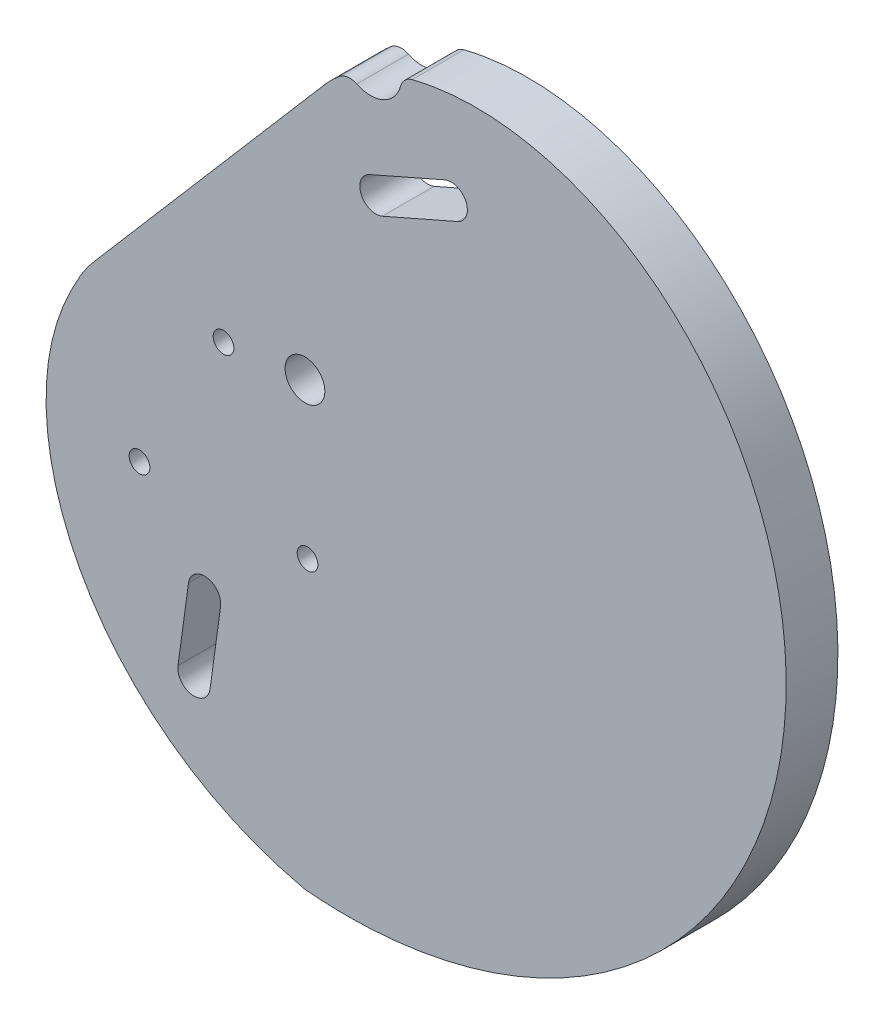
SolidWorks part; units mm, degrees
ref_plane "Front Plane" through (0, 0, 0) normal (0, 0, 1) x (1, 0, 0)
ref_plane "Top Plane" through (0, 0, 0) normal (0, 1, 0) x (1, 0, 0)
ref_plane "Right Plane" through (0, 0, 0) normal (1, 0, 0) x (0, 0, -1)
curve "Curve1"
  spline degree 3 poles (-1.1843, -67.9504, 0) (-0.014, -68.2767, 0) (1.195, -68.3213, 0) (2.3889, -68.4148, 0) (3.5889, -68.4701, 0) (4.791, -68.5105, 0) (5.9959, -68.5295, 0) (7.203, -68.5287, 0) (8.412, -68.5074, 0) (9.6226, -68.4657, 0) (10.8344, -68.4032, 0) (12.047, -68.32, 0) (13.2602, -68.2159, 0) (14.4735, -68.0908, 0) (15.6866, -67.9446, 0) (16.8991, -67.777, 0) (18.1106, -67.5882, 0) (19.3207, -67.3779, 0) (20.529, -67.1461, 0) (21.7351, -66.8927, 0) (22.9386, -66.6176, 0) (24.1392, -66.3208, 0) (25.3362, -66.0022, 0) (26.5295, -65.6619, 0) (27.7184, -65.2996, 0) (28.9026, -64.9155, 0) (30.0816, -64.5096, 0) (31.2551, -64.0817, 0) (32.4225, -63.632, 0) (33.5833, -63.1604, 0) (34.7372, -62.667, 0) (35.8837, -62.1518, 0) (37.0223, -61.6149, 0) (38.1525, -61.0563, 0) (39.2739, -60.4761, 0) (40.3861, -59.8743, 0) (41.4885, -59.2512, 0) (42.5806, -58.6068, 0) (43.6621, -57.9411, 0) (44.7324, -57.2544, 0) (45.791, -56.5468, 0) (46.8375, -55.8184, 0) (47.8714, -55.0695, 0) (48.8923, -54.3001, 0) (49.8996, -53.5105, 0) (50.8929, -52.7009, 0) (51.8717, -51.8715, 0) (52.8356, -51.0225, 0) (53.7841, -50.1542, 0) (54.7166, -49.2668, 0) (55.6329, -48.3607, 0) (56.5323, -47.436, 0) (57.4145, -46.4932, 0) (58.279, -45.5324, 0) (59.1254, -44.554, 0) (59.9531, -43.5583, 0) (60.7619, -42.5458, 0) (61.5512, -41.5167, 0) (62.3207, -40.4714, 0) (63.0698, -39.4103, 0) (63.7983, -38.3338, 0) (64.5057, -37.2423, 0) (65.1916, -36.1362, 0) (65.8556, -35.016, 0) (66.4973, -33.882, 0) (67.1165, -32.7348, 0) (67.7126, -31.5748, 0) (68.2854, -30.4026, 0) (68.8345, -29.2185, 0) (69.3596, -28.023, 0) (69.8603, -26.8168, 0) (70.3364, -25.6003, 0) (70.7876, -24.3741, 0) (71.2134, -23.1386, 0) (71.6138, -21.8945, 0) (71.9884, -20.6423, 0) (72.337, -19.3826, 0) (72.6592, -18.116, 0) (72.955, -16.843, 0) (73.224, -15.5643, 0) (73.4661, -14.2804, 0) (73.6812, -12.992, 0) (73.8689, -11.6997, 0) (74.0292, -10.4042, 0) (74.1619, -9.106, 0) (74.2669, -7.8058, 0) (74.3441, -6.5043, 0) (74.3933, -5.2021, 0) (74.4146, -3.9, 0) (74.4078, -2.5984, 0) (74.3729, -1.2982, 0) (74.3098, -0.0001, 0) (74.2186, 1.2954, 0) (74.0993, 2.5875, 0) (73.9518, 3.8756, 0) (73.7762, 5.1589, 0) (73.5725, 6.4367, 0) (73.3409, 7.7084, 0) (73.0814, 8.9732, 0) (72.7942, 10.2305, 0) (72.4792, 11.4795, 0) (72.1368, 12.7196, 0) (71.767, 13.95, 0) (71.3701, 15.1701, 0) (70.9462, 16.3792, 0) (70.4955, 17.5765, 0) (70.0184, 18.7613, 0) (69.515, 19.9331, 0) (68.9856, 21.091, 0) (68.4305, 22.2344, 0) (67.85, 23.3626, 0) (67.2445, 24.475, 0) (66.6143, 25.5709, 0) (65.9598, 26.6495, 0) (65.2813, 27.7103, 0) (64.5793, 28.7526, 0) (63.8542, 29.7758, 0) (63.1064, 30.7792, 0) (62.3364, 31.7621, 0) (61.5447, 32.7241, 0) (60.7318, 33.6643, 0) (59.8981, 34.5824, 0) (59.0442, 35.4776, 0) (58.1707, 36.3494, 0) (57.2782, 37.1972, 0) (56.3671, 38.0204, 0) (55.4383, 38.8186, 0) (54.4923, 39.5913, 0) (53.53, 40.3381, 0) (52.552, 41.0585, 0) (51.5591, 41.7521, 0) (50.552, 42.4186, 0) (49.5315, 43.0576, 0) (48.4984, 43.6687, 0) (47.4535, 44.2516, 0) (46.3974, 44.8061, 0) (45.3311, 45.3318, 0) (44.2553, 45.8284, 0) (43.1709, 46.2958, 0) (42.0786, 46.7338, 0) (40.9793, 47.1421, 0) (39.8737, 47.5205, 0) (38.7628, 47.869, 0) (37.6473, 48.1874, 0) (36.5281, 48.4755, 0) (35.4061, 48.7334, 0) (34.282, 48.961, 0) (33.1567, 49.1581, 0) (32.031, 49.3249, 0) (30.9059, 49.4613, 0) (29.7821, 49.5673, 0) (28.6604, 49.6431, 0) (27.5418, 49.6886, 0) (26.427, 49.7041, 0) (25.3169, 49.6895, 0) (24.2124, 49.6451, 0) (23.1141, 49.571, 0) (22.0231, 49.4674, 0) (20.94, 49.3346, 0) (19.8657, 49.1727, 0) (18.801, 48.982, 0) (17.7468, 48.7628, 0) (16.7037, 48.5154, 0) (15.6726, 48.2401, 0) (14.6543, 47.9373, 0) (13.6495, 47.6073, 0) (12.659, 47.2504, 0) (11.6836, 46.8672, 0) (10.7239, 46.458, 0) (9.7807, 46.0233, 0) (8.8547, 45.5635, 0) (7.9467, 45.0791, 0) (7.0573, 44.5706, 0) (6.1871, 44.0386, 0) (5.3369, 43.4835, 0) (4.5074, 42.906, 0) (3.699, 42.3065, 0) (2.9126, 41.6858, 0) (2.1491, 41.0448, 0) (1.4087, 40.3857, 0) (0.692, 39.711, 0) (-0.0007, 39.0233, 0) (-0.6692, 38.3252, 0) (-1.3135, 37.6192, 0) (-1.9336, 36.908, 0) (-2.5298, 36.194, 0) (-3.1024, 35.4799, 0) (-3.6521, 34.7682, 0) (-4.1795, 34.0612, 0) (-4.6854, 33.3616, 0) (-5.1709, 32.6716, 0) (-5.637, 31.9937, 0) (-6.085, 31.3301, 0) (-6.5163, 30.6831, 0) (-6.9325, 30.0548, 0) (-7.3352, 29.4474, 0) (-7.7263, 28.8629, 0) (-8.1078, 28.3032, 0) (-8.4816, 27.77, 0) (-8.8501, 27.2652, 0) (-9.216, 26.7897, 0) (-9.5801, 26.3424, 0) (-9.9432, 25.9213, 0) (-10.3062, 25.5243, 0) (-10.6698, 25.1494, 0) (-11.0346, 24.7946, 0) (-11.4009, 24.4578, 0) (-11.7691, 24.1369, 0) (-12.1394, 23.8299, 0) (-12.5117, 23.5348, 0) (-12.8861, 23.2497, 0) (-13.2622, 22.9725, 0) (-13.6397, 22.7014, 0) (-14.0182, 22.4345, 0) (-14.3971, 22.1699, 0) (-14.7757, 21.906, 0) (-15.1531, 21.6409, 0) (-15.5285, 21.3732, 0) (-15.9009, 21.1012, 0) (-16.269, 20.8234, 0) (-16.6317, 20.5384, 0) (-16.9875, 20.2449, 0) (-17.3351, 19.9417, 0) (-17.6745, 19.6295, 0) (-18.0059, 19.3089, 0) (-18.3295, 18.9807, 0) (-18.6455, 18.6455, 0) (-18.9542, 18.3039, 0) (-19.2559, 17.9565, 0) (-19.5509, 17.6038, 0) (-19.8396, 17.2464, 0) (-20.1224, 16.8848, 0) (-20.3997, 16.5195, 0) (-20.672, 16.1508, 0) (-20.9397, 15.7793, 0) (-21.2033, 15.4052, 0) (-21.4634, 15.0289, 0) (-21.7205, 14.6507, 0) (-21.9753, 14.2708, 0) (-22.2281, 13.8895, 0) (-22.4798, 13.507, 0) (-22.7308, 13.1233, 0) (-22.9819, 12.7386, 0) (-23.2336, 12.3529, 0) (-23.4866, 11.9663, 0) (-23.7416, 11.5787, 0) (-23.9993, 11.19, 0) (-24.2602, 10.8001, 0) (-24.5251, 10.4088, 0) (-24.7947, 10.016, 0) (-25.0696, 9.6214, 0) (-25.3504, 9.2246, 0) (-25.6379, 8.8254, 0) (-25.9327, 8.4234, 0) (-26.2354, 8.018, 0) (-26.5467, 7.609, 0) (-26.8672, 7.1956, 0) (-27.1974, 6.7776, 0) (-27.537, 6.3539, 0) (-27.8856, 5.9238, 0) (-28.2424, 5.4864, 0) (-28.6069, 5.0408, 0) (-28.9783, 4.5865, 0) (-29.3562, 4.1226, 0) (-29.7396, 3.6485, 0) (-30.1278, 3.1637, 0) (-30.5202, 2.6674, 0) (-30.9158, 2.1592, 0) (-31.314, 1.6386, 0) (-31.7137, 1.1051, 0) (-32.1143, 0.5583, 0) (-32.5148, -0.0021, 0) (-32.9143, -0.5765, 0) (-33.3119, -1.1651, 0) (-33.7067, -1.7682, 0) (-34.0978, -2.3859, 0) (-34.4843, -3.0184, 0) (-34.8652, -3.6658, 0) (-35.2396, -4.3281, 0) (-35.6066, -5.0053, 0) (-35.9651, -5.6973, 0) (-36.3143, -6.404, 0) (-36.6531, -7.1254, 0) (-36.9808, -7.8611, 0) (-37.2963, -8.611, 0) (-37.5988, -9.3748, 0) (-37.8873, -10.1521, 0) (-38.1609, -10.9426, 0) (-38.4187, -11.7459, 0) (-38.66, -12.5613, 0) (-38.8837, -13.3886, 0) (-39.0892, -14.2271, 0) (-39.2755, -15.0762, 0) (-39.4422, -15.9354, 0) (-39.589, -16.8043, 0) (-39.7155, -17.6823, 0) (-39.8215, -18.5689, 0) (-39.9067, -19.4636, 0) (-39.9709, -20.366, 0) (-40.0137, -21.2755, 0) (-40.035, -22.1916, 0) (-40.0345, -23.1138, 0) (-40.0119, -24.0415, 0) (-39.9672, -24.9742, 0) (-39.9002, -25.9114, 0) (-39.8105, -26.8525, 0) (-39.6982, -27.7969, 0) (-39.563, -28.7442, 0) (-39.4048, -29.6936, 0) (-39.2235, -30.6448, 0) (-39.019, -31.597, 0) (-38.7911, -32.5497, 0) (-38.5399, -33.5023, 0) (-38.2653, -34.4543, 0) (-37.9672, -35.4051, 0) (-37.6456, -36.354, 0) (-37.3004, -37.3005, 0) (-36.9317, -38.2441, 0) (-36.5395, -39.184, 0) (-36.1238, -40.1197, 0) (-35.6847, -41.0507, 0) (-35.2221, -41.9763, 0) (-34.7363, -42.896, 0) (-34.2272, -43.8091, 0) (-33.695, -44.715, 0) (-33.1398, -45.6133, 0) (-32.5617, -46.5032, 0) (-31.9609, -47.3843, 0) (-31.3375, -48.2559, 0) (-30.6917, -49.1174, 0) (-30.0238, -49.9683, 0) (-29.3338, -50.808, 0) (-28.6221, -51.636, 0) (-27.8888, -52.4517, 0) (-27.1343, -53.2545, 0) (-26.3587, -54.0439, 0) (-25.5624, -54.8193, 0) (-24.7457, -55.5802, 0) (-23.9088, -56.3261, 0) (-23.0521, -57.0564, 0) (-22.1759, -57.7707, 0) (-21.2805, -58.4684, 0) (-20.3664, -59.149, 0) (-19.4339, -59.812, 0) (-18.4833, -60.4569, 0) (-17.5151, -61.0833, 0) (-16.5298, -61.6908, 0) (-15.5276, -62.2787, 0) (-14.5091, -62.8467, 0) (-13.4747, -63.3944, 0) (-12.4248, -63.9213, 0) (-11.36, -64.4271, 0) (-10.2807, -64.9112, 0) (-9.1874, -65.3733, 0) (-8.0806, -65.8131, 0) (-6.9608, -66.2301, 0) (-5.8286, -66.6239, 0) (-4.6845, -66.9947, 0) (-3.5289, -67.3403, 0) (-2.3631, -67.6669, 0) (-1.1843, -67.9504, 0) (-0.014, -68.2767, 0) (1.195, -68.3213, 0) knots -0.0101 -0.006743 -0.003377 0 0.00332 0.006645 0.009976 0.013312 0.016655 0.020003 0.023357 0.026716 0.030082 0.033453 0.036831 0.040214 0.043603 0.046998 0.050399 0.053806 0.057218 0.060637 0.064061 0.067491 0.070927 0.074369 0.077816 0.081269 0.084728 0.088192 0.091662 0.095138 0.098619 0.102105 0.105597 0.109094 0.112596 0.116103 0.119615 0.123133 0.126655 0.130182 0.133714 0.137251 0.140792 0.144337 0.147888 0.151442 0.155 0.158563 0.16213 0.1657 0.169275 0.172853 0.176434 0.180019 0.183607 0.187199 0.190793 0.19439 0.19799 0.201593 0.205199 0.208806 0.212416 0.216028 0.219642 0.223258 0.226875 0.230494 0.234115 0.237736 0.241359 0.244982 0.248606 0.252231 0.255856 0.259481 0.263106 0.266731 0.270356 0.273981 0.277605 0.281228 0.28485 0.28847 0.29209 0.295708 0.299324 0.302939 0.306551 0.310161 0.313769 0.317374 0.320976 0.324575 0.328171 0.331763 0.335352 0.338938 0.342519 0.346096 0.349669 0.353237 0.356801 0.360359 0.363913 0.367461 0.371004 0.374541 0.378073 0.381598 0.385117 0.38863 0.392136 0.395636 0.399128 0.402614 0.406092 0.409563 0.413026 0.416482 0.419929 0.423369 0.4268 0.430223 0.433637 0.437043 0.44044 0.443828 0.447206 0.450575 0.453935 0.457284 0.460624 0.463953 0.467272 0.47058 0.473877 0.477164 0.480439 0.483703 0.486955 0.490196 0.493426 0.496643 0.499848 0.503042 0.506223 0.509391 0.512547 0.515691 0.518822 0.52194 0.525045 0.528137 0.531216 0.534282 0.537335 0.540375 0.543401 0.546414 0.549414 0.5524 0.555374 0.558333 0.56128 0.564213 0.567133 0.57004 0.572933 0.575814 0.578681 0.581535 0.584377 0.587205 0.590021 0.592825 0.595616 0.598394 0.60116 0.603911 0.606642 0.60935 0.612032 0.614684 0.617303 0.619884 0.622424 0.62492 0.627367 0.629763 0.632104 0.634387 0.636609 0.638767 0.640858 0.64288 0.644831 0.64671 0.648517 0.65025 0.651911 0.653509 0.655048 0.656538 0.657984 0.659394 0.660772 0.662125 0.663458 0.664774 0.666078 0.667373 0.668662 0.669946 0.671227 0.672507 0.673786 0.675065 0.676344 0.677623 0.678903 0.680182 0.681461 0.68274 0.684019 0.685298 0.686575 0.687853 0.689129 0.690404 0.691679 0.692952 0.694224 0.695495 0.696765 0.698035 0.699304 0.700572 0.70184 0.703109 0.704379 0.705651 0.706925 0.708202 0.709483 0.71077 0.712063 0.713364 0.714674 0.715995 0.717328 0.718676 0.72004 0.721422 0.722825 0.72425 0.7257 0.727177 0.728683 0.730218 0.731784 0.73338 0.735008 0.736668 0.738359 0.740082 0.741837 0.743623 0.745441 0.747291 0.749171 0.751082 0.753022 0.754993 0.756992 0.759021 0.761077 0.76316 0.765271 0.767407 0.769569 0.771756 0.773967 0.776201 0.778458 0.780736 0.783036 0.785357 0.787697 0.790056 0.792433 0.794828 0.797239 0.799666 0.80211 0.804571 0.807047 0.80954 0.812049 0.814575 0.817116 0.819674 0.822248 0.824838 0.827444 0.830066 0.832704 0.835358 0.838027 0.840713 0.843414 0.846131 0.848864 0.851612 0.854376 0.857155 0.859949 0.862759 0.865584 0.868424 0.871279 0.874149 0.877033 0.879933 0.882847 0.885776 0.88872 0.891678 0.89465 0.897636 0.900637 0.903651 0.906679 0.909721 0.912777 0.915847 0.91893 0.922026 0.925135 0.928258 0.931393 0.934541 0.937702 0.940876 0.944062 0.947261 0.950471 0.953694 0.956929 0.960175 0.963433 0.966703 0.969984 0.973276 0.976579 0.979893 0.983218 0.986554 0.9899 0.993257 0.996623 1 1.00332 1.006645 1.009976 periodic
sketch "Sketch1" plane through (0, 0, 0) normal (0, 0, 1) x (1, 0, 0)
  line L0 (10.9805, 30.1851) -> (22.6104, 35.2876) construction
  line L1 (9.976, 32.4744) -> (21.6059, 37.5769)
  line L2 (11.9849, 27.8957) -> (23.6148, 32.9983)
  line L3 (10.7688, 46.4724) -> (16.7954, 32.7363) construction
  line L4 (10.1171, 47.9579) -> (5.632, 46.1692) construction
  line L5 (14.4291, 50.1309) -> (10.1171, 47.9579) construction
  circle A0 centre (0, 0) radius 3.075
  arc A1 (9.976, 32.4744) -> (11.9849, 27.8957) centre (10.9805, 30.1851) ccw
  arc A2 (23.6148, 32.9983) -> (21.6059, 37.5769) centre (22.6104, 35.2876) ccw
  arc A3 (5.632, 46.1692) -> (14.4291, 50.1309) centre (10.1171, 47.9579) ccw
  spline S0 degree 3 poles (-1.1843, -67.9504) (-0.014, -68.2767) (1.195, -68.3213) (2.3889, -68.4148) (3.5889, -68.4701) (4.791, -68.5105) (5.9959, -68.5295) (7.203, -68.5287) (8.412, -68.5074) (9.6226, -68.4657) (10.8344, -68.4032) (12.047, -68.32) (13.2602, -68.2159) (14.4735, -68.0908) (15.6866, -67.9446) (16.8991, -67.777) (18.1106, -67.5882) (19.3207, -67.3779) (20.529, -67.1461) (21.7351, -66.8927) (22.9386, -66.6176) (24.1392, -66.3208) (25.3362, -66.0022) (26.5295, -65.6619) (27.7184, -65.2996) (28.9026, -64.9155) (30.0816, -64.5096) (31.2551, -64.0817) (32.4225, -63.632) (33.5833, -63.1604) (34.7372, -62.667) (35.8837, -62.1518) (37.0223, -61.6149) (38.1525, -61.0563) (39.2739, -60.4761) (40.3861, -59.8743) (41.4885, -59.2512) (42.5806, -58.6068) (43.6621, -57.9411) (44.7324, -57.2544) (45.791, -56.5468) (46.8375, -55.8184) (47.8714, -55.0695) (48.8923, -54.3001) (49.8996, -53.5105) (50.8929, -52.7009) (51.8717, -51.8715) (52.8356, -51.0225) (53.7841, -50.1542) (54.7166, -49.2668) (55.6329, -48.3607) (56.5323, -47.436) (57.4145, -46.4932) (58.279, -45.5324) (59.1254, -44.554) (59.9531, -43.5583) (60.7619, -42.5458) (61.5512, -41.5167) (62.3207, -40.4714) (63.0698, -39.4103) (63.7983, -38.3338) (64.5057, -37.2423) (65.1916, -36.1362) (65.8556, -35.016) (66.4973, -33.882) (67.1165, -32.7348) (67.7126, -31.5748) (68.2854, -30.4026) (68.8345, -29.2185) (69.3596, -28.023) (69.8603, -26.8168) (70.3364, -25.6003) (70.7876, -24.3741) (71.2134, -23.1386) (71.6138, -21.8945) (71.9884, -20.6423) (72.337, -19.3826) (72.6592, -18.116) (72.955, -16.843) (73.224, -15.5643) (73.4661, -14.2804) (73.6812, -12.992) (73.8689, -11.6997) (74.0292, -10.4042) (74.1619, -9.106) (74.2669, -7.8058) (74.3441, -6.5043) (74.3933, -5.2021) (74.4146, -3.9) (74.4078, -2.5984) (74.3729, -1.2982) (74.3098, -0.0001) (74.2186, 1.2954) (74.0993, 2.5875) (73.9518, 3.8756) (73.7762, 5.1589) (73.5725, 6.4367) (73.3409, 7.7084) (73.0814, 8.9732) (72.7942, 10.2305) (72.4792, 11.4795) (72.1368, 12.7196) (71.767, 13.95) (71.3701, 15.1701) (70.9462, 16.3792) (70.4955, 17.5765) (70.0184, 18.7613) (69.515, 19.9331) (68.9856, 21.091) (68.4305, 22.2344) (67.85, 23.3626) (67.2445, 24.475) (66.6143, 25.5709) (65.9598, 26.6495) (65.2813, 27.7103) (64.5793, 28.7526) (63.8542, 29.7758) (63.1064, 30.7792) (62.3364, 31.7621) (61.5447, 32.7241) (60.7318, 33.6643) (59.8981, 34.5824) (59.0442, 35.4776) (58.1707, 36.3494) (57.2782, 37.1972) (56.3671, 38.0204) (55.4383, 38.8186) (54.4923, 39.5913) (53.53, 40.3381) (52.552, 41.0585) (51.5591, 41.7521) (50.552, 42.4186) (49.5315, 43.0576) (48.4984, 43.6687) (47.4535, 44.2516) (46.3974, 44.8061) (45.3311, 45.3318) (44.2553, 45.8284) (43.1709, 46.2958) (42.0786, 46.7338) (40.9793, 47.1421) (39.8737, 47.5205) (38.7628, 47.869) (37.6473, 48.1874) (36.5281, 48.4755) (35.4061, 48.7334) (34.282, 48.961) (33.1567, 49.1581) (32.031, 49.3249) (30.9059, 49.4613) (29.7821, 49.5673) (28.6604, 49.6431) (27.5418, 49.6886) (26.427, 49.7041) (25.3169, 49.6895) (24.2124, 49.6451) (23.1141, 49.571) (22.0231, 49.4674) (20.94, 49.3346) (19.8657, 49.1727) (18.801, 48.982) (17.7468, 48.7628) (16.7037, 48.5154) (15.6726, 48.2401) (14.6543, 47.9373) (13.6495, 47.6073) (12.659, 47.2504) (11.6836, 46.8672) (10.7239, 46.458) (9.7807, 46.0233) (8.8547, 45.5635) (7.9467, 45.0791) (7.0573, 44.5706) (6.1871, 44.0386) (5.3369, 43.4835) (4.5074, 42.906) (3.699, 42.3065) (2.9126, 41.6858) (2.1491, 41.0448) (1.4087, 40.3857) (0.692, 39.711) (-0.0007, 39.0233) (-0.6692, 38.3252) (-1.3135, 37.6192) (-1.9336, 36.908) (-2.5298, 36.194) (-3.1024, 35.4799) (-3.6521, 34.7682) (-4.1795, 34.0612) (-4.6854, 33.3616) (-5.1709, 32.6716) (-5.637, 31.9937) (-6.085, 31.3301) (-6.5163, 30.6831) (-6.9325, 30.0548) (-7.3352, 29.4474) (-7.7263, 28.8629) (-8.1078, 28.3032) (-8.4816, 27.77) (-8.8501, 27.2652) (-9.216, 26.7897) (-9.5801, 26.3424) (-9.9432, 25.9213) (-10.3062, 25.5243) (-10.6698, 25.1494) (-11.0346, 24.7946) (-11.4009, 24.4578) (-11.7691, 24.1369) (-12.1394, 23.8299) (-12.5117, 23.5348) (-12.8861, 23.2497) (-13.2622, 22.9725) (-13.6397, 22.7014) (-14.0182, 22.4345) (-14.3971, 22.1699) (-14.7757, 21.906) (-15.1531, 21.6409) (-15.5285, 21.3732) (-15.9009, 21.1012) (-16.269, 20.8234) (-16.6317, 20.5384) (-16.9875, 20.2449) (-17.3351, 19.9417) (-17.6745, 19.6295) (-18.0059, 19.3089) (-18.3295, 18.9807) (-18.6455, 18.6455) (-18.9542, 18.3039) (-19.2559, 17.9565) (-19.5509, 17.6038) (-19.8396, 17.2464) (-20.1224, 16.8848) (-20.3997, 16.5195) (-20.672, 16.1508) (-20.9397, 15.7793) (-21.2033, 15.4052) (-21.4634, 15.0289) (-21.7205, 14.6507) (-21.9753, 14.2708) (-22.2281, 13.8895) (-22.4798, 13.507) (-22.7308, 13.1233) (-22.9819, 12.7386) (-23.2336, 12.3529) (-23.4866, 11.9663) (-23.7416, 11.5787) (-23.9993, 11.19) (-24.2602, 10.8001) (-24.5251, 10.4088) (-24.7947, 10.016) (-25.0696, 9.6214) (-25.3504, 9.2246) (-25.6379, 8.8254) (-25.9327, 8.4234) (-26.2354, 8.018) (-26.5467, 7.609) (-26.8672, 7.1956) (-27.1974, 6.7776) (-27.537, 6.3539) (-27.8856, 5.9238) (-28.2424, 5.4864) (-28.6069, 5.0408) (-28.9783, 4.5865) (-29.3562, 4.1226) (-29.7396, 3.6485) (-30.1278, 3.1637) (-30.5202, 2.6674) (-30.9158, 2.1592) (-31.314, 1.6386) (-31.7137, 1.1051) (-32.1143, 0.5583) (-32.5148, -0.0021) (-32.9143, -0.5765) (-33.3119, -1.1651) (-33.7067, -1.7682) (-34.0978, -2.3859) (-34.4843, -3.0184) (-34.8652, -3.6658) (-35.2396, -4.3281) (-35.6066, -5.0053) (-35.9651, -5.6973) (-36.3143, -6.404) (-36.6531, -7.1254) (-36.9808, -7.8611) (-37.2963, -8.611) (-37.5988, -9.3748) (-37.8873, -10.1521) (-38.1609, -10.9426) (-38.4187, -11.7459) (-38.66, -12.5613) (-38.8837, -13.3886) (-39.0892, -14.2271) (-39.2755, -15.0762) (-39.4422, -15.9354) (-39.589, -16.8043) (-39.7155, -17.6823) (-39.8215, -18.5689) (-39.9067, -19.4636) (-39.9709, -20.366) (-40.0137, -21.2755) (-40.035, -22.1916) (-40.0345, -23.1138) (-40.0119, -24.0415) (-39.9672, -24.9742) (-39.9002, -25.9114) (-39.8105, -26.8525) (-39.6982, -27.7969) (-39.563, -28.7442) (-39.4048, -29.6936) (-39.2235, -30.6448) (-39.019, -31.597) (-38.7911, -32.5497) (-38.5399, -33.5023) (-38.2653, -34.4543) (-37.9672, -35.4051) (-37.6456, -36.354) (-37.3004, -37.3005) (-36.9317, -38.2441) (-36.5395, -39.184) (-36.1238, -40.1197) (-35.6847, -41.0507) (-35.2221, -41.9763) (-34.7363, -42.896) (-34.2272, -43.8091) (-33.695, -44.715) (-33.1398, -45.6133) (-32.5617, -46.5032) (-31.9609, -47.3843) (-31.3375, -48.2559) (-30.6917, -49.1174) (-30.0238, -49.9683) (-29.3338, -50.808) (-28.6221, -51.636) (-27.8888, -52.4517) (-27.1343, -53.2545) (-26.3587, -54.0439) (-25.5624, -54.8193) (-24.7457, -55.5802) (-23.9088, -56.3261) (-23.0521, -57.0564) (-22.1759, -57.7707) (-21.2805, -58.4684) (-20.3664, -59.149) (-19.4339, -59.812) (-18.4833, -60.4569) (-17.5151, -61.0833) (-16.5298, -61.6908) (-15.5276, -62.2787) (-14.5091, -62.8467) (-13.4747, -63.3944) (-12.4248, -63.9213) (-11.36, -64.4271) (-10.2807, -64.9112) (-9.1874, -65.3733) (-8.0806, -65.8131) (-6.9608, -66.2301) (-5.8286, -66.6239) (-4.6845, -66.9947) (-3.5289, -67.3403) (-2.3631, -67.6669) (-1.1843, -67.9504) (-0.014, -68.2767) (1.195, -68.3213) knots -0.0101 -0.006743 -0.003377 0 0.00332 0.006645 0.009976 0.013312 0.016655 0.020003 0.023357 0.026716 0.030082 0.033453 0.036831 0.040214 0.043603 0.046998 0.050399 0.053806 0.057218 0.060637 0.064061 0.067491 0.070927 0.074369 0.077816 0.081269 0.084728 0.088192 0.091662 0.095138 0.098619 0.102105 0.105597 0.109094 0.112596 0.116103 0.119615 0.123133 0.126655 0.130182 0.133714 0.137251 0.140792 0.144337 0.147888 0.151442 0.155 0.158563 0.16213 0.1657 0.169275 0.172853 0.176434 0.180019 0.183607 0.187199 0.190793 0.19439 0.19799 0.201593 0.205199 0.208806 0.212416 0.216028 0.219642 0.223258 0.226875 0.230494 0.234115 0.237736 0.241359 0.244982 0.248606 0.252231 0.255856 0.259481 0.263106 0.266731 0.270356 0.273981 0.277605 0.281228 0.28485 0.28847 0.29209 0.295708 0.299324 0.302939 0.306551 0.310161 0.313769 0.317374 0.320976 0.324575 0.328171 0.331763 0.335352 0.338938 0.342519 0.346096 0.349669 0.353237 0.356801 0.360359 0.363913 0.367461 0.371004 0.374541 0.378073 0.381598 0.385117 0.38863 0.392136 0.395636 0.399128 0.402614 0.406092 0.409563 0.413026 0.416482 0.419929 0.423369 0.4268 0.430223 0.433637 0.437043 0.44044 0.443828 0.447206 0.450575 0.453935 0.457284 0.460624 0.463953 0.467272 0.47058 0.473877 0.477164 0.480439 0.483703 0.486955 0.490196 0.493426 0.496643 0.499848 0.503042 0.506223 0.509391 0.512547 0.515691 0.518822 0.52194 0.525045 0.528137 0.531216 0.534282 0.537335 0.540375 0.543401 0.546414 0.549414 0.5524 0.555374 0.558333 0.56128 0.564213 0.567133 0.57004 0.572933 0.575814 0.578681 0.581535 0.584377 0.587205 0.590021 0.592825 0.595616 0.598394 0.60116 0.603911 0.606642 0.60935 0.612032 0.614684 0.617303 0.619884 0.622424 0.62492 0.627367 0.629763 0.632104 0.634387 0.636609 0.638767 0.640858 0.64288 0.644831 0.64671 0.648517 0.65025 0.651911 0.653509 0.655048 0.656538 0.657984 0.659394 0.660772 0.662125 0.663458 0.664774 0.666078 0.667373 0.668662 0.669946 0.671227 0.672507 0.673786 0.675065 0.676344 0.677623 0.678903 0.680182 0.681461 0.68274 0.684019 0.685298 0.686575 0.687853 0.689129 0.690404 0.691679 0.692952 0.694224 0.695495 0.696765 0.698035 0.699304 0.700572 0.70184 0.703109 0.704379 0.705651 0.706925 0.708202 0.709483 0.71077 0.712063 0.713364 0.714674 0.715995 0.717328 0.718676 0.72004 0.721422 0.722825 0.72425 0.7257 0.727177 0.728683 0.730218 0.731784 0.73338 0.735008 0.736668 0.738359 0.740082 0.741837 0.743623 0.745441 0.747291 0.749171 0.751082 0.753022 0.754993 0.756992 0.759021 0.761077 0.76316 0.765271 0.767407 0.769569 0.771756 0.773967 0.776201 0.778458 0.780736 0.783036 0.785357 0.787697 0.790056 0.792433 0.794828 0.797239 0.799666 0.80211 0.804571 0.807047 0.80954 0.812049 0.814575 0.817116 0.819674 0.822248 0.824838 0.827444 0.830066 0.832704 0.835358 0.838027 0.840713 0.843414 0.846131 0.848864 0.851612 0.854376 0.857155 0.859949 0.862759 0.865584 0.868424 0.871279 0.874149 0.877033 0.879933 0.882847 0.885776 0.88872 0.891678 0.89465 0.897636 0.900637 0.903651 0.906679 0.909721 0.912777 0.915847 0.91893 0.922026 0.925135 0.928258 0.931393 0.934541 0.937702 0.940876 0.944062 0.947261 0.950471 0.953694 0.956929 0.960175 0.963433 0.966703 0.969984 0.973276 0.976579 0.979893 0.983218 0.986554 0.9899 0.993257 0.996623 1 1.00332 1.006645 1.009976 only from (0, -68.2309) to (0, -68.2309) construction
  spline S1 degree 3 poles (-1.1843, -67.9504) (-0.014, -68.2767) (1.195, -68.3213) (2.3889, -68.4148) (3.5889, -68.4701) (4.791, -68.5105) (5.9959, -68.5295) (7.203, -68.5287) (8.412, -68.5074) (9.6226, -68.4657) (10.8344, -68.4032) (12.047, -68.32) (13.2602, -68.2159) (14.4735, -68.0908) (15.6866, -67.9446) (16.8991, -67.777) (18.1106, -67.5882) (19.3207, -67.3779) (20.529, -67.1461) (21.7351, -66.8927) (22.9386, -66.6176) (24.1392, -66.3208) (25.3362, -66.0022) (26.5295, -65.6619) (27.7184, -65.2996) (28.9026, -64.9155) (30.0816, -64.5096) (31.2551, -64.0817) (32.4225, -63.632) (33.5833, -63.1604) (34.7372, -62.667) (35.8837, -62.1518) (37.0223, -61.6149) (38.1525, -61.0563) (39.2739, -60.4761) (40.3861, -59.8743) (41.4885, -59.2512) (42.5806, -58.6068) (43.6621, -57.9411) (44.7324, -57.2544) (45.791, -56.5468) (46.8375, -55.8184) (47.8714, -55.0695) (48.8923, -54.3001) (49.8996, -53.5105) (50.8929, -52.7009) (51.8717, -51.8715) (52.8356, -51.0225) (53.7841, -50.1542) (54.7166, -49.2668) (55.6329, -48.3607) (56.5323, -47.436) (57.4145, -46.4932) (58.279, -45.5324) (59.1254, -44.554) (59.9531, -43.5583) (60.7619, -42.5458) (61.5512, -41.5167) (62.3207, -40.4714) (63.0698, -39.4103) (63.7983, -38.3338) (64.5057, -37.2423) (65.1916, -36.1362) (65.8556, -35.016) (66.4973, -33.882) (67.1165, -32.7348) (67.7126, -31.5748) (68.2854, -30.4026) (68.8345, -29.2185) (69.3596, -28.023) (69.8603, -26.8168) (70.3364, -25.6003) (70.7876, -24.3741) (71.2134, -23.1386) (71.6138, -21.8945) (71.9884, -20.6423) (72.337, -19.3826) (72.6592, -18.116) (72.955, -16.843) (73.224, -15.5643) (73.4661, -14.2804) (73.6812, -12.992) (73.8689, -11.6997) (74.0292, -10.4042) (74.1619, -9.106) (74.2669, -7.8058) (74.3441, -6.5043) (74.3933, -5.2021) (74.4146, -3.9) (74.4078, -2.5984) (74.3729, -1.2982) (74.3098, -0.0001) (74.2186, 1.2954) (74.0993, 2.5875) (73.9518, 3.8756) (73.7762, 5.1589) (73.5725, 6.4367) (73.3409, 7.7084) (73.0814, 8.9732) (72.7942, 10.2305) (72.4792, 11.4795) (72.1368, 12.7196) (71.767, 13.95) (71.3701, 15.1701) (70.9462, 16.3792) (70.4955, 17.5765) (70.0184, 18.7613) (69.515, 19.9331) (68.9856, 21.091) (68.4305, 22.2344) (67.85, 23.3626) (67.2445, 24.475) (66.6143, 25.5709) (65.9598, 26.6495) (65.2813, 27.7103) (64.5793, 28.7526) (63.8542, 29.7758) (63.1064, 30.7792) (62.3364, 31.7621) (61.5447, 32.7241) (60.7318, 33.6643) (59.8981, 34.5824) (59.0442, 35.4776) (58.1707, 36.3494) (57.2782, 37.1972) (56.3671, 38.0204) (55.4383, 38.8186) (54.4923, 39.5913) (53.53, 40.3381) (52.552, 41.0585) (51.5591, 41.7521) (50.552, 42.4186) (49.5315, 43.0576) (48.4984, 43.6687) (47.4535, 44.2516) (46.3974, 44.8061) (45.3311, 45.3318) (44.2553, 45.8284) (43.1709, 46.2958) (42.0786, 46.7338) (40.9793, 47.1421) (39.8737, 47.5205) (38.7628, 47.869) (37.6473, 48.1874) (36.5281, 48.4755) (35.4061, 48.7334) (34.282, 48.961) (33.1567, 49.1581) (32.031, 49.3249) (30.9059, 49.4613) (29.7821, 49.5673) (28.6604, 49.6431) (27.5418, 49.6886) (26.427, 49.7041) (25.3169, 49.6895) (24.2124, 49.6451) (23.1141, 49.571) (22.0231, 49.4674) (20.94, 49.3346) (19.8657, 49.1727) (18.801, 48.982) (17.7468, 48.7628) (16.7037, 48.5154) (15.6726, 48.2401) (14.6543, 47.9373) (13.6495, 47.6073) (12.659, 47.2504) (11.6836, 46.8672) (10.7239, 46.458) (9.7807, 46.0233) (8.8547, 45.5635) (7.9467, 45.0791) (7.0573, 44.5706) (6.1871, 44.0386) (5.3369, 43.4835) (4.5074, 42.906) (3.699, 42.3065) (2.9126, 41.6858) (2.1491, 41.0448) (1.4087, 40.3857) (0.692, 39.711) (-0.0007, 39.0233) (-0.6692, 38.3252) (-1.3135, 37.6192) (-1.9336, 36.908) (-2.5298, 36.194) (-3.1024, 35.4799) (-3.6521, 34.7682) (-4.1795, 34.0612) (-4.6854, 33.3616) (-5.1709, 32.6716) (-5.637, 31.9937) (-6.085, 31.3301) (-6.5163, 30.6831) (-6.9325, 30.0548) (-7.3352, 29.4474) (-7.7263, 28.8629) (-8.1078, 28.3032) (-8.4816, 27.77) (-8.8501, 27.2652) (-9.216, 26.7897) (-9.5801, 26.3424) (-9.9432, 25.9213) (-10.3062, 25.5243) (-10.6698, 25.1494) (-11.0346, 24.7946) (-11.4009, 24.4578) (-11.7691, 24.1369) (-12.1394, 23.8299) (-12.5117, 23.5348) (-12.8861, 23.2497) (-13.2622, 22.9725) (-13.6397, 22.7014) (-14.0182, 22.4345) (-14.3971, 22.1699) (-14.7757, 21.906) (-15.1531, 21.6409) (-15.5285, 21.3732) (-15.9009, 21.1012) (-16.269, 20.8234) (-16.6317, 20.5384) (-16.9875, 20.2449) (-17.3351, 19.9417) (-17.6745, 19.6295) (-18.0059, 19.3089) (-18.3295, 18.9807) (-18.6455, 18.6455) (-18.9542, 18.3039) (-19.2559, 17.9565) (-19.5509, 17.6038) (-19.8396, 17.2464) (-20.1224, 16.8848) (-20.3997, 16.5195) (-20.672, 16.1508) (-20.9397, 15.7793) (-21.2033, 15.4052) (-21.4634, 15.0289) (-21.7205, 14.6507) (-21.9753, 14.2708) (-22.2281, 13.8895) (-22.4798, 13.507) (-22.7308, 13.1233) (-22.9819, 12.7386) (-23.2336, 12.3529) (-23.4866, 11.9663) (-23.7416, 11.5787) (-23.9993, 11.19) (-24.2602, 10.8001) (-24.5251, 10.4088) (-24.7947, 10.016) (-25.0696, 9.6214) (-25.3504, 9.2246) (-25.6379, 8.8254) (-25.9327, 8.4234) (-26.2354, 8.018) (-26.5467, 7.609) (-26.8672, 7.1956) (-27.1974, 6.7776) (-27.537, 6.3539) (-27.8856, 5.9238) (-28.2424, 5.4864) (-28.6069, 5.0408) (-28.9783, 4.5865) (-29.3562, 4.1226) (-29.7396, 3.6485) (-30.1278, 3.1637) (-30.5202, 2.6674) (-30.9158, 2.1592) (-31.314, 1.6386) (-31.7137, 1.1051) (-32.1143, 0.5583) (-32.5148, -0.0021) (-32.9143, -0.5765) (-33.3119, -1.1651) (-33.7067, -1.7682) (-34.0978, -2.3859) (-34.4843, -3.0184) (-34.8652, -3.6658) (-35.2396, -4.3281) (-35.6066, -5.0053) (-35.9651, -5.6973) (-36.3143, -6.404) (-36.6531, -7.1254) (-36.9808, -7.8611) (-37.2963, -8.611) (-37.5988, -9.3748) (-37.8873, -10.1521) (-38.1609, -10.9426) (-38.4187, -11.7459) (-38.66, -12.5613) (-38.8837, -13.3886) (-39.0892, -14.2271) (-39.2755, -15.0762) (-39.4422, -15.9354) (-39.589, -16.8043) (-39.7155, -17.6823) (-39.8215, -18.5689) (-39.9067, -19.4636) (-39.9709, -20.366) (-40.0137, -21.2755) (-40.035, -22.1916) (-40.0345, -23.1138) (-40.0119, -24.0415) (-39.9672, -24.9742) (-39.9002, -25.9114) (-39.8105, -26.8525) (-39.6982, -27.7969) (-39.563, -28.7442) (-39.4048, -29.6936) (-39.2235, -30.6448) (-39.019, -31.597) (-38.7911, -32.5497) (-38.5399, -33.5023) (-38.2653, -34.4543) (-37.9672, -35.4051) (-37.6456, -36.354) (-37.3004, -37.3005) (-36.9317, -38.2441) (-36.5395, -39.184) (-36.1238, -40.1197) (-35.6847, -41.0507) (-35.2221, -41.9763) (-34.7363, -42.896) (-34.2272, -43.8091) (-33.695, -44.715) (-33.1398, -45.6133) (-32.5617, -46.5032) (-31.9609, -47.3843) (-31.3375, -48.2559) (-30.6917, -49.1174) (-30.0238, -49.9683) (-29.3338, -50.808) (-28.6221, -51.636) (-27.8888, -52.4517) (-27.1343, -53.2545) (-26.3587, -54.0439) (-25.5624, -54.8193) (-24.7457, -55.5802) (-23.9088, -56.3261) (-23.0521, -57.0564) (-22.1759, -57.7707) (-21.2805, -58.4684) (-20.3664, -59.149) (-19.4339, -59.812) (-18.4833, -60.4569) (-17.5151, -61.0833) (-16.5298, -61.6908) (-15.5276, -62.2787) (-14.5091, -62.8467) (-13.4747, -63.3944) (-12.4248, -63.9213) (-11.36, -64.4271) (-10.2807, -64.9112) (-9.1874, -65.3733) (-8.0806, -65.8131) (-6.9608, -66.2301) (-5.8286, -66.6239) (-4.6845, -66.9947) (-3.5289, -67.3403) (-2.3631, -67.6669) (-1.1843, -67.9504) (-0.014, -68.2767) (1.195, -68.3213) knots -0.0101 -0.006743 -0.003377 0 0.00332 0.006645 0.009976 0.013312 0.016655 0.020003 0.023357 0.026716 0.030082 0.033453 0.036831 0.040214 0.043603 0.046998 0.050399 0.053806 0.057218 0.060637 0.064061 0.067491 0.070927 0.074369 0.077816 0.081269 0.084728 0.088192 0.091662 0.095138 0.098619 0.102105 0.105597 0.109094 0.112596 0.116103 0.119615 0.123133 0.126655 0.130182 0.133714 0.137251 0.140792 0.144337 0.147888 0.151442 0.155 0.158563 0.16213 0.1657 0.169275 0.172853 0.176434 0.180019 0.183607 0.187199 0.190793 0.19439 0.19799 0.201593 0.205199 0.208806 0.212416 0.216028 0.219642 0.223258 0.226875 0.230494 0.234115 0.237736 0.241359 0.244982 0.248606 0.252231 0.255856 0.259481 0.263106 0.266731 0.270356 0.273981 0.277605 0.281228 0.28485 0.28847 0.29209 0.295708 0.299324 0.302939 0.306551 0.310161 0.313769 0.317374 0.320976 0.324575 0.328171 0.331763 0.335352 0.338938 0.342519 0.346096 0.349669 0.353237 0.356801 0.360359 0.363913 0.367461 0.371004 0.374541 0.378073 0.381598 0.385117 0.38863 0.392136 0.395636 0.399128 0.402614 0.406092 0.409563 0.413026 0.416482 0.419929 0.423369 0.4268 0.430223 0.433637 0.437043 0.44044 0.443828 0.447206 0.450575 0.453935 0.457284 0.460624 0.463953 0.467272 0.47058 0.473877 0.477164 0.480439 0.483703 0.486955 0.490196 0.493426 0.496643 0.499848 0.503042 0.506223 0.509391 0.512547 0.515691 0.518822 0.52194 0.525045 0.528137 0.531216 0.534282 0.537335 0.540375 0.543401 0.546414 0.549414 0.5524 0.555374 0.558333 0.56128 0.564213 0.567133 0.57004 0.572933 0.575814 0.578681 0.581535 0.584377 0.587205 0.590021 0.592825 0.595616 0.598394 0.60116 0.603911 0.606642 0.60935 0.612032 0.614684 0.617303 0.619884 0.622424 0.62492 0.627367 0.629763 0.632104 0.634387 0.636609 0.638767 0.640858 0.64288 0.644831 0.64671 0.648517 0.65025 0.651911 0.653509 0.655048 0.656538 0.657984 0.659394 0.660772 0.662125 0.663458 0.664774 0.666078 0.667373 0.668662 0.669946 0.671227 0.672507 0.673786 0.675065 0.676344 0.677623 0.678903 0.680182 0.681461 0.68274 0.684019 0.685298 0.686575 0.687853 0.689129 0.690404 0.691679 0.692952 0.694224 0.695495 0.696765 0.698035 0.699304 0.700572 0.70184 0.703109 0.704379 0.705651 0.706925 0.708202 0.709483 0.71077 0.712063 0.713364 0.714674 0.715995 0.717328 0.718676 0.72004 0.721422 0.722825 0.72425 0.7257 0.727177 0.728683 0.730218 0.731784 0.73338 0.735008 0.736668 0.738359 0.740082 0.741837 0.743623 0.745441 0.747291 0.749171 0.751082 0.753022 0.754993 0.756992 0.759021 0.761077 0.76316 0.765271 0.767407 0.769569 0.771756 0.773967 0.776201 0.778458 0.780736 0.783036 0.785357 0.787697 0.790056 0.792433 0.794828 0.797239 0.799666 0.80211 0.804571 0.807047 0.80954 0.812049 0.814575 0.817116 0.819674 0.822248 0.824838 0.827444 0.830066 0.832704 0.835358 0.838027 0.840713 0.843414 0.846131 0.848864 0.851612 0.854376 0.857155 0.859949 0.862759 0.865584 0.868424 0.871279 0.874149 0.877033 0.879933 0.882847 0.885776 0.88872 0.891678 0.89465 0.897636 0.900637 0.903651 0.906679 0.909721 0.912777 0.915847 0.91893 0.922026 0.925135 0.928258 0.931393 0.934541 0.937702 0.940876 0.944062 0.947261 0.950471 0.953694 0.956929 0.960175 0.963433 0.966703 0.969984 0.973276 0.976579 0.979893 0.983218 0.986554 0.9899 0.993257 0.996623 1 1.00332 1.006645 1.009976 only from (0, -68.2309) to (0, -68.2309)
  point P6 (16.7954, 32.7363)
  dimension "D1" = 6.15
  dimension "D5" = 4.8286
  dimension "D6" = 174.997
  dimension "D2" = 12.7
  dimension "D3" = 5
  dimension "D4" = 15
extrude "Boss-Extrude1" add sketch "Sketch1" along normal mid plane 8 contours A3 S1 A0 A2 L2 A1 L1 region at (18.9558, -11.7959, 0)
sketch "Sketch2" plane through (0, 0, 0) normal (0, 0, 1) x (1, 0, 0)
  line L0 (4.833, 43.1309) -> (-33.6653, -1.7073)
  line L1 (-33.6653, -1.7073) -> (-6.8619, 43.1309)
  line L2 (-6.8619, 43.1309) -> (4.833, 43.1309)
extrude "Cut-Extrude1" cut sketch "Sketch2" against normal through all both and the other way through all
fillet "Fillet1" radius 20 2 edges at (-33.6653, -1.7073, 0) (4.833, 43.1309, 0)
sketch "Sketch3" plane through (0, 0, 4) normal (0, 0, 1) x (1, 0, 0)
  point P0 (-12.5939, -1.2726)
  point P1 (0.3965, -23.7726)
  point P3 (-25.5843, -23.7726)
hole_wizard "M4x0.7 Tapped Hole1" positions "Sketch4" profile "Sketch5" tap size "M4x0.7" standard "ANSI Metric" end condition through all
sketch "Sketch4" plane through (0, 0, 4) normal (0, 0, 1) x (1, 0, 0)
  point P0 (-12.5939, -1.2726)
  point P3 (0.3965, -23.7726)
  point P6 (-25.5843, -23.7726)
sketch "Sketch5" plane through (-12.5939, -1.2726, 4) normal (1, 0, 0) x (0, -1, 0)
  line L0 (0, 0) -> (0, 8)
  line L1 (0, 8) -> (1.6, 8)
  line L2 (1.6, 8) -> (1.6, 0)
  line L5 (1.6, 0) -> (0, 0)
  line L11 (0, -6.35) -> (0, 107.95) construction
  dimension "Thru Tap Drill Dia." = 3.2
  dimension "Thru Tap Drill Depth" = 8
fillet "Fillet2" radius 2.5 2 edges at (14.9453, 48.0218, 0) (6.8246, 44.4259, 0)
sketch "Sketch6" plane through (0, 0, 4) normal (0, 0, 1) x (1, 0, 0)
  line L0 (-15.5247, -36.542) -> (-17.1545, -48.4308) construction
  line L1 (-13.0454, -36.8819) -> (-14.6752, -48.7707)
  line L2 (-18.0039, -36.2021) -> (-19.6337, -48.0909)
  arc A0 (-13.0454, -36.8819) -> (-18.0039, -36.2021) centre (-15.5247, -36.542) ccw
  arc A1 (-19.6337, -48.0909) -> (-14.6752, -48.7707) centre (-17.1545, -48.4308) ccw
  point P4 (-16.3396, -42.4864)
  dimension "D1" = 2.5024
extrude "Cut-Extrude2" cut sketch "Sketch6" against normal blind 10 contours L1 A1 L2 A0
